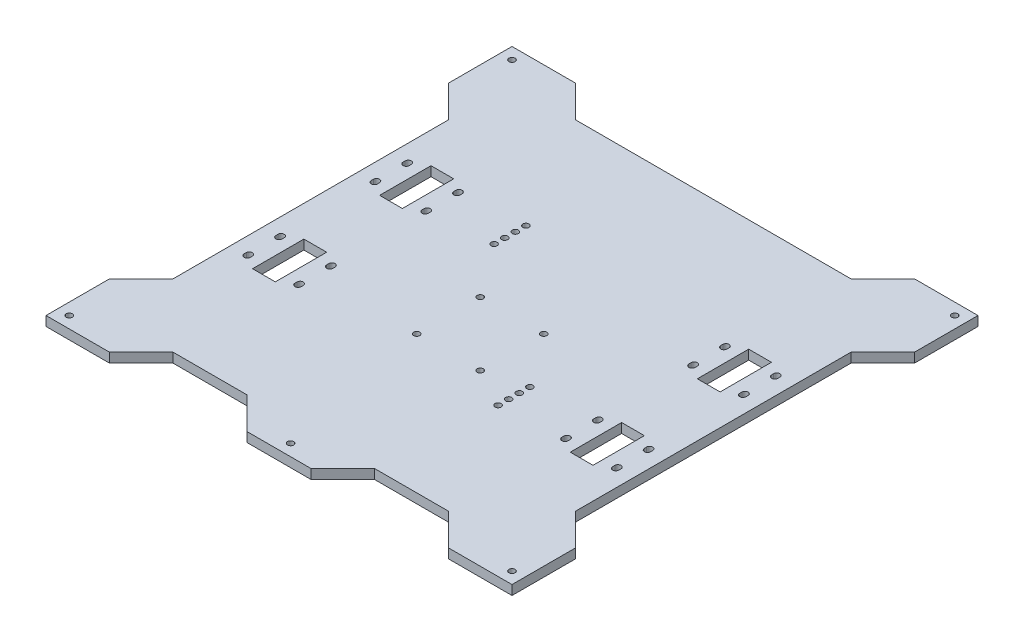
SolidWorks part; units mm, degrees
ref_plane "Front Plane" through (0, 0, 0) normal (0, 0, 1) x (1, 0, 0)
ref_plane "Top Plane" through (0, 0, 0) normal (0, 1, 0) x (1, 0, 0)
ref_plane "Right Plane" through (0, 0, 0) normal (1, 0, 0) x (0, 0, -1)
sketch "Sketch1" plane through (0, 0, 0) normal (0, 1, 0) x (1, 0, 0)
  line L1 (-110, 110) -> (110, 110)
  line L2 (-110, 110) -> (-110, -110)
  line L3 (-110, -110) -> (110, -110)
  line L4 (110, 110) -> (110, -110)
  line L5 (-110, 110) -> (110, -110) construction
  line L6 (-110, -110) -> (110, 110) construction
  point P0 (0, 0)
  dimension "D1" = 220
  dimension "D2" = 220
extrude "Square" add sketch "Sketch1" along normal blind 4.5
sketch "Sketch2" plane through (0, 4.5, 0) normal (0, 1, 0) x (1, 0, 0)
  line L0 (0, 110) -> (0, -110) construction
  line L1 (110, 110) -> (-110, 110) construction
  line L2 (-110, -110) -> (110, -110) construction
  line L3 (-110, 0) -> (110, 0) construction
  line L4 (-110, 110) -> (-110, -110) construction
  line L5 (110, -110) -> (110, 110) construction
  line L6 (75, 110) -> (75, -110) construction
  line L7 (75, 30) -> (0, 30) construction
  line L8 (75, -30) -> (0, -30) construction
  circle A0 centre (87, 38) radius 1.45
  circle A1 centre (87, 22) radius 1.45
  circle A2 centre (63, 22) radius 1.45
  circle A3 centre (63, 38) radius 1.45
  circle A4 centre (-63, 38) radius 1.45
  circle A5 centre (-63, 22) radius 1.45
  circle A6 centre (-87, 22) radius 1.45
  circle A7 centre (-87, 38) radius 1.45
  circle A8 centre (-87, 22) radius 1.45
  circle A9 centre (-87, 38) radius 1.45
  circle A10 centre (-63, 38) radius 1.45
  circle A11 centre (-63, 22) radius 1.45
  circle A12 centre (63, 22) radius 1.45
  circle A13 centre (63, 38) radius 1.45
  circle A14 centre (87, 38) radius 1.45
  circle A15 centre (87, 22) radius 1.45
  circle A16 centre (87, -22) radius 1.45
  circle A17 centre (87, -38) radius 1.45
  circle A18 centre (63, -38) radius 1.45
  circle A19 centre (63, -22) radius 1.45
  circle A20 centre (-63, -22) radius 1.45
  circle A21 centre (-63, -38) radius 1.45
  circle A22 centre (-87, -38) radius 1.45
  circle A23 centre (-87, -22) radius 1.45
  circle A24 centre (-87, -38) radius 1.45
  circle A25 centre (-87, -22) radius 1.45
  circle A26 centre (-63, -22) radius 1.45
  circle A27 centre (-63, -38) radius 1.45
  circle A28 centre (63, -38) radius 1.45
  circle A29 centre (63, -22) radius 1.45
  circle A30 centre (87, -22) radius 1.45
  circle A31 centre (87, -38) radius 1.45
  dimension "D6" = 2.9
  dimension "D7" = 2.9
  dimension "D1" = 75
  dimension "D2" = 30
  dimension "D3" = 16
  dimension "D5" = 12
extrude "LM8UU-Holders" cut sketch "Sketch2" against normal through all contours A7 | A6 | A5 | A4 | A20 | A21 | A22 | A23 | A19 | A18 | A17 | A16 | A1 | A0 | A3 | A2 region at (87, 4.5, -38) region at (87, 4.5, -22) region at (63, 4.5, -22) region at (63, 4.5, -38) region at (-63, 4.5, -38) region at (-63, 4.5, -22) region at (-87, 4.5, -22) region at (-87, 4.5, -38) region at (87, 4.5, 22) region at (87, 4.5, 38) region at (63, 4.5, 38) region at (63, 4.5, 22) region at (-63, 4.5, 22) region at (-63, 4.5, 38) region at (-87, 4.5, 38) region at (-87, 4.5, 22)
sketch "Sketch10" plane through (0, 4.5, 0) normal (0, 1, 0) x (1, 0, 0)
  line L0 (0, 110) -> (0, -79.9796) construction
  line L3 (-26.5242, 0) -> (110, 0) construction
  line L6 (75, 110) -> (75, -110) construction
  line L7 (75, 30) -> (-75, 30) construction
  line L8 (87, 22) -> (87, 23) construction
  line L9 (110, 110) -> (-110, 110) construction
  line L10 (110, -110) -> (110, 110) construction
  line L11 (85.55, 22) -> (85.55, 23)
  line L12 (88.45, 22) -> (88.45, 23)
  line L13 (87, 38) -> (87, 37) construction
  line L14 (88.45, 38) -> (88.45, 37)
  line L15 (85.55, 38) -> (85.55, 37)
  line L16 (63, 38) -> (63, 37) construction
  line L17 (61.55, 38) -> (61.55, 37)
  line L18 (64.45, 38) -> (64.45, 37)
  line L19 (63, 22) -> (63, 23) construction
  line L20 (64.45, 22) -> (64.45, 23)
  line L21 (61.55, 22) -> (61.55, 23)
  line L22 (75, -30) -> (-75, -30) construction
  line L23 (87, -22) -> (87, -23) construction
  line L24 (85.55, -22) -> (85.55, -23)
  line L25 (88.45, -22) -> (88.45, -23)
  line L26 (87, -38) -> (87, -37) construction
  line L27 (88.45, -38) -> (88.45, -37)
  line L28 (85.55, -38) -> (85.55, -37)
  line L29 (63, -38) -> (63, -37) construction
  line L30 (61.55, -38) -> (61.55, -37)
  line L31 (64.45, -38) -> (64.45, -37)
  line L32 (63, -22) -> (63, -23) construction
  line L33 (64.45, -22) -> (64.45, -23)
  line L34 (61.55, -22) -> (61.55, -23)
  line L35 (26.5242, 0) -> (-110, 0) construction
  line L36 (-87, 22) -> (-87, 23) construction
  line L37 (-85.55, 22) -> (-85.55, 23)
  line L38 (-88.45, 22) -> (-88.45, 23)
  line L39 (-87, 38) -> (-87, 37) construction
  line L40 (-88.45, 38) -> (-88.45, 37)
  line L41 (-85.55, 38) -> (-85.55, 37)
  line L42 (-63, 38) -> (-63, 37) construction
  line L43 (-61.55, 38) -> (-61.55, 37)
  line L44 (-64.45, 38) -> (-64.45, 37)
  line L45 (-63, 22) -> (-63, 23) construction
  line L46 (-64.45, 22) -> (-64.45, 23)
  line L47 (-61.55, 22) -> (-61.55, 23)
  line L48 (-87, -22) -> (-87, -23) construction
  line L49 (-85.55, -22) -> (-85.55, -23)
  line L50 (-88.45, -22) -> (-88.45, -23)
  line L51 (-87, -38) -> (-87, -37) construction
  line L52 (-88.45, -38) -> (-88.45, -37)
  line L53 (-85.55, -38) -> (-85.55, -37)
  line L54 (-63, -38) -> (-63, -37) construction
  line L55 (-61.55, -38) -> (-61.55, -37)
  line L56 (-64.45, -38) -> (-64.45, -37)
  line L57 (-63, -22) -> (-63, -23) construction
  line L58 (-64.45, -22) -> (-64.45, -23)
  line L59 (-61.55, -22) -> (-61.55, -23)
  arc A0 (61.55, 38) -> (64.45, 38) centre (63, 38) cw
  arc A1 (88.45, 38) -> (85.55, 38) centre (87, 38) ccw
  arc A2 (85.55, 22) -> (88.45, 22) centre (87, 22) ccw
  arc A3 (88.45, 23) -> (85.55, 23) centre (87, 23) ccw
  arc A4 (85.55, 37) -> (88.45, 37) centre (87, 37) ccw
  arc A5 (64.45, 37) -> (61.55, 37) centre (63, 37) cw
  arc A6 (64.45, 22) -> (61.55, 22) centre (63, 22) cw
  arc A7 (61.55, 23) -> (64.45, 23) centre (63, 23) cw
  arc A8 (85.55, -22) -> (88.45, -22) centre (87, -22) cw
  arc A9 (88.45, -23) -> (85.55, -23) centre (87, -23) cw
  arc A10 (88.45, -38) -> (85.55, -38) centre (87, -38) cw
  arc A11 (85.55, -37) -> (88.45, -37) centre (87, -37) cw
  arc A12 (61.55, -38) -> (64.45, -38) centre (63, -38) ccw
  arc A13 (64.45, -37) -> (61.55, -37) centre (63, -37) ccw
  arc A14 (64.45, -22) -> (61.55, -22) centre (63, -22) ccw
  arc A15 (61.55, -23) -> (64.45, -23) centre (63, -23) ccw
  arc A16 (-85.55, 22) -> (-88.45, 22) centre (-87, 22) cw
  arc A17 (-88.45, 23) -> (-85.55, 23) centre (-87, 23) cw
  arc A18 (-88.45, 38) -> (-85.55, 38) centre (-87, 38) cw
  arc A19 (-85.55, 37) -> (-88.45, 37) centre (-87, 37) cw
  arc A20 (-61.55, 38) -> (-64.45, 38) centre (-63, 38) ccw
  arc A21 (-64.45, 37) -> (-61.55, 37) centre (-63, 37) ccw
  arc A22 (-64.45, 22) -> (-61.55, 22) centre (-63, 22) ccw
  arc A23 (-61.55, 23) -> (-64.45, 23) centre (-63, 23) ccw
  arc A24 (-85.55, -22) -> (-88.45, -22) centre (-87, -22) ccw
  arc A25 (-88.45, -23) -> (-85.55, -23) centre (-87, -23) ccw
  arc A26 (-88.45, -38) -> (-85.55, -38) centre (-87, -38) ccw
  arc A27 (-85.55, -37) -> (-88.45, -37) centre (-87, -37) ccw
  arc A28 (-61.55, -38) -> (-64.45, -38) centre (-63, -38) cw
  arc A29 (-64.45, -37) -> (-61.55, -37) centre (-63, -37) cw
  arc A30 (-64.45, -22) -> (-61.55, -22) centre (-63, -22) cw
  arc A31 (-61.55, -23) -> (-64.45, -23) centre (-63, -23) cw
  point P8 (87, 22.5)
  point P19 (87, 37.5)
  point P28 (63, 37.5)
  point P35 (63, 22.5)
  point P44 (87, -22.5)
  point P51 (87, -37.5)
  point P58 (63, -37.5)
  point P65 (63, -22.5)
  point P73 (0, 30)
  point P74 (0, -30)
  point P76 (-87, 22.5)
  point P83 (-87, 37.5)
  point P90 (-63, 37.5)
  point P97 (-63, 22.5)
  point P104 (-87, -22.5)
  point P111 (-87, -37.5)
  point P118 (-63, -37.5)
  point P125 (-63, -22.5)
  dimension "D1" = 75
  dimension "D2" = 30
  dimension "D3" = 16
  dimension "D5" = 12
  dimension "D4" = 1.45
  dimension "D7" = 1.45
sketch "Sketch3" plane through (0, 4.5, 0) normal (0, 1, 0) x (1, 0, 0)
  line L0 (0, -110) -> (0, 110) construction
  line L1 (-110, -110) -> (110, -110) construction
  line L2 (110, 110) -> (-110, 110) construction
  line L3 (110, -15) -> (-110, -15) construction
  line L6 (15, -30) -> (-15, -30) construction
  line L7 (15, 0) -> (-15, 0) construction
  line L8 (110, -110) -> (110, 110) construction
  line L9 (-110, 110) -> (-110, -110) construction
  line L10 (110, 0) -> (-110, 0) construction
  circle A0 centre (-15, -30) radius 1.45
  circle A1 centre (15, -30) radius 1.45
  circle A2 centre (15, 0) radius 1.45
  circle A3 centre (-15, 0) radius 1.45
  point P16 (0, -30)
  dimension "D1" = 2.9
  dimension "D2" = 15
  dimension "D3" = 15
  dimension "D5" = 15
extrude "DefaultBelt" cut sketch "Sketch3" against normal through all
sketch "Sketch4" plane through (0, 4.5, 0) normal (0, 1, 0) x (1, 0, 0)
  line L0 (0, 110) -> (0, -110) construction
  line L1 (110, 110) -> (-110, 110) construction
  line L2 (-110, -110) -> (110, -110) construction
  line L3 (-15, -1.45) -> (-15, -28.55) construction
  line L4 (15, -28.55) -> (15, -1.45) construction
  line L5 (15, -15) -> (-15, -15) construction
  arc A0 (-0.7348, 6.25) -> (0.7348, 6.25) centre (0, 5) ccw
  arc A1 (0.7348, 6.25) -> (-0.7348, 6.25) centre (0, 7.5) ccw
  arc A2 (0.7348, -36.25) -> (-0.7348, -36.25) centre (0, -37.5) cw
  arc A3 (-0.7348, -36.25) -> (0.7348, -36.25) centre (0, -35) cw
  circle A4 centre (-15, 0) radius 1.45 construction
  circle A5 centre (-15, -30) radius 1.45 construction
  circle A6 centre (15, -30) radius 1.45 construction
  circle A7 centre (15, 0) radius 1.45 construction
  dimension "D1" = 2.9
  dimension "D2" = 2.9
  dimension "D3" = 20
  dimension "D4" = 22.5
extrude "BeltOptions" [suppressed] cut sketch "Sketch4" against normal through all
sketch "Sketch5" plane through (0, 4.5, 0) normal (0, 1, 0) x (1, 0, 0)
  line L0 (-110, 0) -> (110, 0) construction
  line L1 (-110, 110) -> (-110, -110) construction
  line L2 (110, -110) -> (110, 110) construction
  line L3 (0, 110) -> (0, -110) construction
  line L4 (110, 110) -> (-110, 110) construction
  line L5 (-110, 110) -> (-110, 80)
  line L6 (-110, 80) -> (-95, 65)
  line L7 (-95, 65) -> (-95, -65)
  line L8 (0, 0) -> (-110, 110) construction
  line L9 (-65, 95) -> (65, 95)
  line L10 (-80, 110) -> (-65, 95)
  line L11 (-110, 110) -> (-80, 110)
  line L12 (-95, 65) -> (-95, -65)
  line L13 (0, 0) -> (110, 110) construction
  line L14 (95, 65) -> (95, -65)
  line L15 (110, 110) -> (80, 110)
  line L16 (80, 110) -> (65, 95)
  line L17 (95, 65) -> (95, -65)
  line L18 (110, 80) -> (95, 65)
  line L19 (110, 110) -> (110, 80)
  line L20 (0, 0) -> (110, -110) construction
  line L21 (0, 0) -> (-110, -110) construction
  line L22 (110, -110) -> (110, -80)
  line L23 (110, -80) -> (95, -65)
  line L24 (80, -110) -> (65, -95)
  line L25 (110, -110) -> (80, -110)
  line L26 (-110, -110) -> (-80, -110)
  line L27 (-80, -110) -> (-65, -95)
  line L28 (-65, -95) -> (65, -95)
  line L29 (-110, -80) -> (-95, -65)
  line L30 (-110, -110) -> (-110, -80)
  point P24 (0, 95)
  point P32 (95, 0)
  point P35 (-95, 0)
  point P36 (0, -95)
  circle M16 centre (15, -30) radius 1.45
  circle M18 centre (63, 38) radius 1.45
  circle M20 centre (87, 22) radius 1.45
  circle M22 centre (87, -38) radius 1.45
  circle M23 centre (63, -38) radius 1.45
  circle M24 centre (63, -22) radius 1.45
  circle M25 centre (-87, -22) radius 1.45
  circle M26 centre (-87, -38) radius 1.45
  circle M27 centre (-63, -38) radius 1.45
  circle M28 centre (-63, -22) radius 1.45
  circle M29 centre (-63, 38) radius 1.45
  circle M30 centre (-63, 22) radius 1.45
  circle M31 centre (-87, 22) radius 1.45
  circle M32 centre (-87, 38) radius 1.45
  line M33 (110, -110) -> (110, 110)
  line M34 (110, 110) -> (-110, 110)
  line M35 (-110, 110) -> (-110, -110)
  line M36 (-110, -110) -> (110, -110)
  dimension "D1" = 15
  dimension "D2" = 30
  dimension "D3" = 45
  dimension "D4" = 45
extrude "Shaping" cut sketch "Sketch5" against normal blind 10 flip side to cut contours L29 L27 L28 L24 L23 L14 L18 L16 L9 L10 L6 L7 M35 M36 M33 M34 M16 M18 M20 M22 M24 M26 M28 M30 M32 M31 M29 M27 M25 M23 region at (0.037, 4.5, -0.0113)
sketch "Sketch6" plane through (0, 4.5, 0) normal (0, 1, 0) x (1, 0, 0)
  line L0 (-110, 110) -> (110, -110) construction
  line L1 (-110, -110) -> (110, 110) construction
  line L2 (110, 80) -> (110, 110) construction
  line L3 (0, 95) -> (0, -95) construction
  line L4 (-65, 95) -> (65, 95) construction
  line L5 (-65, -95) -> (65, -95) construction
  line L6 (-95, 0) -> (95, 0) construction
  line L7 (-95, 65) -> (-95, -65) construction
  line L8 (95, 65) -> (95, -65) construction
  circle A0 centre (-104.5, 104.5) radius 1.45
  circle A1 centre (104.5, 104.5) radius 1.45
  circle A2 centre (104.5, -104.5) radius 1.45
  circle A3 centre (-104.5, -104.5) radius 1.45
  dimension "D2" = 2.9
  dimension "D1" = 45
  dimension "D3" = 104.5
extrude "Cut-Extrude5" cut sketch "Sketch6" against normal through all
sketch "Sketch7" plane through (0, 4.5, 0) normal (0, 1, 0) x (1, 0, 0)
  line L0 (-87, 38) -> (-63, 22) construction
  line L1 (-63, 22) -> (-87, 22) construction
  line L2 (-87, 22) -> (-63, 38) construction
  line L3 (-63, 38) -> (-87, 38) construction
  line L4 (-95, 0) -> (95, 0) construction
  line L5 (-80.375, 42.125) -> (-69.625, 42.125)
  line L6 (-80.375, 42.125) -> (-80.375, 17.875)
  line L7 (-80.375, 17.875) -> (-69.625, 17.875)
  line L8 (-69.625, 42.125) -> (-69.625, 17.875)
  line L9 (-80.375, 42.125) -> (-69.625, 17.875) construction
  line L10 (-80.375, 17.875) -> (-69.625, 42.125) construction
  line L11 (-95, 65) -> (-95, -65) construction
  line L12 (95, 65) -> (95, -65) construction
  line L13 (0, -95) -> (0, 95) construction
  line L14 (-65, -95) -> (65, -95) construction
  line L15 (-65, 95) -> (65, 95) construction
  line L16 (-80.375, -17.875) -> (-69.625, -42.125) construction
  line L17 (-80.375, -42.125) -> (-69.625, -17.875) construction
  line L18 (-63, -38) -> (-87, -38) construction
  line L19 (-87, -22) -> (-63, -38) construction
  line L20 (-63, -22) -> (-87, -22) construction
  line L21 (-87, -38) -> (-63, -22) construction
  line L22 (-69.625, -42.125) -> (-69.625, -17.875)
  line L23 (-80.375, -17.875) -> (-69.625, -17.875)
  line L24 (-80.375, -42.125) -> (-80.375, -17.875)
  line L25 (-80.375, -42.125) -> (-69.625, -42.125)
  line L26 (-80.375, 17.875) -> (-69.625, 42.125) construction
  line L27 (80.375, 17.875) -> (69.625, 42.125) construction
  line L28 (87, -38) -> (63, -22) construction
  line L29 (63, -22) -> (87, -22) construction
  line L30 (87, -22) -> (63, -38) construction
  line L31 (63, -38) -> (87, -38) construction
  line L32 (80.375, -42.125) -> (69.625, -17.875) construction
  line L33 (80.375, -17.875) -> (69.625, -42.125) construction
  line L34 (80.375, 17.875) -> (69.625, 42.125) construction
  line L35 (80.375, 42.125) -> (69.625, 17.875) construction
  line L36 (63, 38) -> (87, 38) construction
  line L37 (87, 22) -> (63, 38) construction
  line L38 (63, 22) -> (87, 22) construction
  line L39 (87, 38) -> (63, 22) construction
  line L40 (80.375, -42.125) -> (69.625, -42.125)
  line L41 (80.375, -42.125) -> (80.375, -17.875)
  line L42 (80.375, -17.875) -> (69.625, -17.875)
  line L43 (69.625, -42.125) -> (69.625, -17.875)
  line L44 (69.625, 42.125) -> (69.625, 17.875)
  line L45 (80.375, 17.875) -> (69.625, 17.875)
  line L46 (80.375, 42.125) -> (80.375, 17.875)
  line L47 (80.375, 42.125) -> (69.625, 42.125)
  point P4 (-75, 30)
  point P33 (-75, -30)
  point P50 (75, -30)
  point P51 (75, 30)
  dimension "D1" = 10.75
  dimension "D2" = 24.25
extrude "Cut-Extrude6" cut sketch "Sketch7" against normal through all
sketch "Sketch8" plane through (0, 4.5, 0) normal (0, 1, 0) x (1, 0, 0)
  line L0 (0, 0) -> (0, 95) construction
  line L1 (0, 0) -> (-66.8115, 0) construction
  line L2 (-65, -95) -> (65, -95) construction
  line L3 (-65, 95) -> (65, 95) construction
  line L4 (-33.45, 40) -> (-33.45, 25) construction
  line L5 (-33.45, 40) -> (-33.45, 25) construction
  line L6 (33.45, -40) -> (33.45, -25) construction
  circle A0 centre (-33.45, 40) radius 1.45
  circle A1 centre (-33.45, 35) radius 1.45
  circle A2 centre (-33.45, 30) radius 1.45
  circle A3 centre (-33.45, 25) radius 1.45
  circle A8 centre (33.45, -40) radius 1.45
  circle A9 centre (33.45, -35) radius 1.45
  circle A10 centre (33.45, -30) radius 1.45
  circle A11 centre (33.45, -25) radius 1.45
  dimension "D1" = 2.9
  dimension "D11" = 2.9
  dimension "D12" = 2.9
  dimension "D13" = 2.9
  dimension "D14" = 2.9
  dimension "D2" = 55
  dimension "D4" = 33.45
  dimension "D5" = 5
  dimension "D6" = 5
  dimension "D7" = 55
  dimension "D8" = 5
  dimension "D9" = 5
  dimension "D10" = 33.45
extrude "EndstopTrigger" cut sketch "Sketch8" against normal through all
pattern_linear "LPattern1" [suppressed] count 2 spacing 30 of bodies 108
sketch "Sketch9" plane through (0, 4.5, 0) normal (0, 1, 0) x (1, 0, 0)
  line L2 (-80, -110) -> (80, -110) construction
  line L3 (0, -110) -> (0, -95) construction
  line L4 (-104.5, -104.5) -> (104.5, -104.5) construction
  line L5 (15, -110) -> (-15, -110)
  line L6 (-15, -110) -> (-30, -95)
  line L7 (-95, 0) -> (95, 0) construction
  line L8 (-95, 65) -> (-95, -65) construction
  line L9 (-30, -95) -> (30, -95)
  line L10 (15, -110) -> (30, -95)
  line L11 (95, 65) -> (95, -65) construction
  line L12 (-110, -110) -> (-80, -110) construction
  line L13 (-65, -95) -> (65, -95) construction
  line L14 (-80, -110) -> (-65, -95) construction
  line L15 (80, -110) -> (65, -95) construction
  circle A0 centre (0, -104.5) radius 1.45
  circle A3 centre (-104.5, -104.5) radius 1.45 construction
  circle A4 centre (104.5, -104.5) radius 1.45 construction
extrude "Boss-Extrude1" add sketch "Sketch9" against normal through all
extrude "HolesToSlots" cut sketch "Sketch10" against normal through all
sketch "Sketch11" plane through (0, 4.5, 0) normal (0, 1, 0) x (1, 0, 0)
  line L0 (0, -110) -> (0, 0) construction
  line L1 (-65, -95) -> (-30, -95) construction
  line L2 (95, 0) -> (0, 0) construction
  line L3 (95, 65) -> (95, -65) construction
  line L4 (0, 0) -> (110, -110) construction
  line L5 (-69.1421, -85) -> (-5, -85)
  line L6 (-69.1421, -85) -> (-84.1421, -100)
  line L7 (-84.1421, -100) -> (-100, -100)
  line L8 (-100, -100) -> (-100, -84.1421)
  line L9 (-100, -84.1421) -> (-85, -69.1421)
  line L10 (-85, -69.1421) -> (-85, -52.125)
  line L11 (-85, -52.125) -> (-5, -52.125)
  line L12 (-80, -110) -> (-65, -95) construction
  line L13 (-110, -80) -> (-95, -65) construction
  line L14 (-110, -80) -> (-110, -110) construction
  line L15 (-110, -110) -> (-80, -110) construction
  line L16 (-80.375, -42.125) -> (-69.625, -42.125) construction
  line L17 (-95, 65) -> (-95, -65) construction
  line L18 (-5, -52.125) -> (-5, -85)
  line L19 (5, -52.125) -> (5, -85)
  line L20 (85, -52.125) -> (5, -52.125)
  line L21 (85, -69.1421) -> (85, -52.125)
  line L22 (100, -84.1421) -> (85, -69.1421)
  line L23 (100, -100) -> (100, -84.1421)
  line L24 (84.1421, -100) -> (100, -100)
  line L25 (69.1421, -85) -> (84.1421, -100)
  line L26 (69.1421, -85) -> (5, -85)
  line L27 (69.1421, 85) -> (5, 85)
  line L28 (69.1421, 85) -> (84.1421, 100)
  line L29 (84.1421, 100) -> (100, 100)
  line L30 (100, 100) -> (100, 84.1421)
  line L31 (100, 84.1421) -> (85, 69.1421)
  line L32 (85, 69.1421) -> (85, 52.125)
  line L33 (85, 52.125) -> (5, 52.125)
  line L34 (5, 52.125) -> (5, 85)
  line L35 (-5, 52.125) -> (-5, 85)
  line L36 (-85, 52.125) -> (-5, 52.125)
  line L37 (-85, 69.1421) -> (-85, 52.125)
  line L38 (-100, 84.1421) -> (-85, 69.1421)
  line L39 (-100, 100) -> (-100, 84.1421)
  line L40 (-84.1421, 100) -> (-100, 100)
  line L41 (-69.1421, 85) -> (-84.1421, 100)
  line L42 (-69.1421, 85) -> (-5, 85)
  line L43 (-15, -110) -> (15, -110) construction
  dimension "D1" = 10
  dimension "D2" = 10
  dimension "D3" = 10
  dimension "D4" = 10
  dimension "D5" = 10
  dimension "D6" = 10
  dimension "D7" = 10
  dimension "D8" = 5
extrude "Cut-Extrude7" [suppressed] cut sketch "Sketch11" against normal through all
sketch "Sketch12" [suppressed] plane through (0, 4.5, 0) normal (0, 1, 0) x (1, 0, 0)
  line L0 (0, 0) -> (-110, -110) construction
  line L1 (-110, -110) -> (-80, -110) construction
  line L2 (-110, -80) -> (80, 110) construction
  line L3 (110, 80) -> (-80, -110) construction
  line L4 (-95, -65) -> (-65, -95) construction
  line L5 (0, 0) -> (0, -95) construction
  line L6 (-65, -95) -> (65, -95) construction
  line L7 (95, 0) -> (-95, 0) construction
  line L8 (-95, 65) -> (-95, -65) construction
  line L9 (-100, -100) -> (-100, -84.1421)
  line L10 (-100, -84.1421) -> (-59.2893, -43.4315)
  line L11 (-59.2893, -43.4315) -> (-43.4315, -43.4315)
  line L12 (-110, -80) -> (-110, -110) construction
  line L13 (-100, -100) -> (-84.1421, -100)
  line L14 (-84.1421, -100) -> (-43.4315, -59.2893)
  line L15 (-43.4315, -59.2893) -> (-43.4315, -43.4315)
  line L16 (55, -85) -> (-55, -85)
  line L17 (-55, -85) -> (-29.2893, -59.2893)
  line L18 (-29.2893, -59.2893) -> (29.2893, -59.2893)
  line L19 (95, -65) -> (65, -95) construction
  line L20 (0, 0) -> (110, -110) construction
  line L21 (55, -85) -> (29.2893, -59.2893)
  line L22 (43.4315, -59.2893) -> (43.4315, -43.4315)
  line L23 (84.1421, -100) -> (43.4315, -59.2893)
  line L24 (100, -100) -> (84.1421, -100)
  line L25 (59.2893, -43.4315) -> (43.4315, -43.4315)
  line L26 (100, -84.1421) -> (59.2893, -43.4315)
  line L27 (100, -100) -> (100, -84.1421)
  line L28 (95, 65) -> (65, 95) construction
  line L29 (-95, 65) -> (-65, 95) construction
  line L30 (100, 100) -> (100, 84.1421)
  line L31 (100, 84.1421) -> (59.2893, 43.4315)
  line L32 (59.2893, 43.4315) -> (43.4315, 43.4315)
  line L33 (100, 100) -> (84.1421, 100)
  line L34 (84.1421, 100) -> (43.4315, 59.2893)
  line L35 (43.4315, 59.2893) -> (43.4315, 43.4315)
  line L36 (55, 85) -> (29.2893, 59.2893)
  line L37 (-29.2893, 59.2893) -> (29.2893, 59.2893)
  line L38 (-55, 85) -> (-29.2893, 59.2893)
  line L39 (55, 85) -> (-55, 85)
  line L40 (-43.4315, 59.2893) -> (-43.4315, 43.4315)
  line L41 (-84.1421, 100) -> (-43.4315, 59.2893)
  line L42 (-100, 100) -> (-84.1421, 100)
  line L43 (-59.2893, 43.4315) -> (-43.4315, 43.4315)
  line L44 (-100, 84.1421) -> (-59.2893, 43.4315)
  line L45 (-100, 100) -> (-100, 84.1421)
  point P40 (0, -59.2893)
  point P41 (0, -85)
  point P67 (0, 85)
  point P68 (0, 59.2893)
  dimension "D1" = 10
  dimension "D2" = 10
  dimension "D3" = 80
  dimension "D4" = 10
  dimension "D5" = 10
  dimension "D6" = 0
extrude "Cut-Extrude8" [suppressed] cut sketch "Sketch12" against normal through all
sketch "Sketch14" [suppressed] plane through (0, 4.5, 0) normal (0, 1, 0) x (1, 0, 0)
  line L0 (0, 85) -> (0, 110) construction
  line L1 (55, 85) -> (-55, 85) construction
  line L2 (15, 110) -> (-15, 110) construction
  line L3 (10.8579, 100) -> (-10.8579, 100)
  line L4 (-10.8579, 100) -> (-25.8579, 85)
  line L5 (-25.8579, 85) -> (25.8579, 85)
  line L6 (-15, 110) -> (-30, 95) construction
  line L7 (10.8579, 100) -> (25.8579, 85)
  point P13 (0, 100)
  dimension "D1" = 10
  dimension "D2" = 10
extrude "Cut-Extrude10" [suppressed] cut sketch "Sketch14" against normal through all
sketch "Sketch13" [suppressed] plane through (0, 4.5, 0) normal (0, 1, 0) x (1, 0, 0)
  line L0 (-59.2893, 43.4315) -> (-59.2893, -43.4315) construction
  line L1 (-100, 84.1421) -> (-59.2893, 43.4315) construction
  line L2 (-59.2893, 0) -> (0, 0) construction
  line L3 (-59.2893, 33.4315) -> (-59.2893, -33.4315)
  line L4 (-59.2893, -33.4315) -> (-43.4315, -33.4315)
  line L5 (-43.4315, -33.4315) -> (-43.4315, 33.4315)
  line L6 (-43.4315, 33.4315) -> (-59.2893, 33.4315)
  line L7 (-59.2893, 43.4315) -> (-43.4315, 43.4315) construction
  line L8 (-43.4315, -43.4315) -> (-59.2893, -43.4315) construction
  line L9 (-43.4315, 43.4315) -> (-43.4315, 59.2893) construction
  line L10 (0, 0) -> (0, 43.4315) construction
  line L11 (59.2893, 43.4315) -> (59.2893, -43.4315) construction
  line L12 (43.4315, 33.4315) -> (59.2893, 33.4315)
  line L13 (43.4315, -33.4315) -> (43.4315, 33.4315)
  line L14 (59.2893, -33.4315) -> (43.4315, -33.4315)
  line L15 (59.2893, 33.4315) -> (59.2893, -33.4315)
  line L16 (110, -110) -> (0, 0) construction
  line L17 (55, -85) -> (29.2893, -59.2893) construction
  line L18 (-33.4315, -43.2893) -> (33.4315, -43.2893)
  line L19 (-33.4315, -43.2893) -> (-33.4315, -63.4315)
  line L20 (-33.4315, -63.4315) -> (33.4315, -63.4315)
  line L21 (33.4315, -43.2893) -> (33.4315, -63.4315)
  line L22 (-33.4315, -43.2893) -> (33.4315, -63.4315) construction
  line L23 (-33.4315, -63.4315) -> (33.4315, -43.2893) construction
  line L24 (-43.4315, -59.2893) -> (-43.4315, -43.4315) construction
  line L25 (0, -53.3604) -> (0, -63.4315) construction
  line L26 (55, 85) -> (25.8579, 85) construction
  line L28 (43.4315, -43.4315) -> (43.4315, -59.2893) construction
  line L29 (29.2893, -59.2893) -> (-29.2893, -59.2893) construction
  line L30 (43.4315, 59.2893) -> (43.4315, 43.4315) construction
  line L31 (-33.4315, 83) -> (33.4315, 83)
  line L32 (-33.4315, 83) -> (-33.4315, 15)
  line L33 (-33.4315, 15) -> (33.4315, 15)
  line L34 (33.4315, 83) -> (33.4315, 15)
  line L35 (-33.4315, 83) -> (33.4315, 15) construction
  line L36 (-33.4315, 15) -> (33.4315, 83) construction
  point P27 (0, -53.3604)
  point P43 (0, 49)
  dimension "D1" = 10
  dimension "D2" = 10
  dimension "D3" = 10
  dimension "D4" = 10
  dimension "D5" = 16
  dimension "D6" = 10
  dimension "D7" = 10
  dimension "D8" = 15
  dimension "D9" = 2
extrude "Cut-Extrude9" [suppressed] cut sketch "Sketch13" against normal through all
sketch "Sketch15" [suppressed] plane through (0, 4.5, 0) normal (0, 1, 0) x (1, 0, 0)
  line L0 (-59.2893, 0) -> (-95, 0) construction
  line L1 (-59.2893, 33.4315) -> (-59.2893, -33.4315) construction
  line L2 (-95, 65) -> (-95, -65) construction
  line L3 (-80.5, 17.875) -> (-69.5, 17.875) construction
  line L4 (-59.2893, -15) -> (-59.2893, -7.875)
  line L5 (-85, -7.875) -> (-85, 7.875)
  line L6 (-85, 7.875) -> (-66.4143, 7.875)
  line L7 (-59.2893, -7.875) -> (-59.2893, 7.875)
  line L8 (-66.4143, -7.875) -> (-59.2893, -15)
  line L9 (-85, -7.875) -> (-66.4143, -7.875)
  line L11 (-66.4143, 7.875) -> (-59.2893, 15)
  line L12 (-59.2893, 15) -> (-59.2893, 7.875)
  line L13 (0, 0) -> (0, -21.7485) construction
  line L14 (59.2893, 0) -> (95, 0) construction
  line L15 (59.2893, 15) -> (59.2893, 7.875)
  line L16 (66.4143, 7.875) -> (59.2893, 15)
  line L17 (85, -7.875) -> (66.4143, -7.875)
  line L18 (66.4143, -7.875) -> (59.2893, -15)
  line L19 (59.2893, -7.875) -> (59.2893, 7.875)
  line L20 (85, 7.875) -> (66.4143, 7.875)
  line L21 (85, -7.875) -> (85, 7.875)
  line L22 (59.2893, -15) -> (59.2893, -7.875)
  line L23 (-59.2893, 0) -> (-95, 0) construction
  point P17 (-85, 0)
  point P30 (85, 0)
  dimension "D1" = 10
  dimension "D2" = 10
  dimension "D4" = 45
  dimension "D5" = 15
extrude "Cut-Extrude11" [suppressed] cut sketch "Sketch15" against normal through all
sketch "Sketch16" [suppressed] plane through (0, 4.5, 0) normal (0, 1, 0) x (1, 0, 0)
  line L0 (-85, -69.1421) -> (-85, -52.125)
  line L1 (-59.2893, -43.4315) -> (-100, -84.1421) construction
  line L2 (-85, -52.125) -> (-67.9829, -52.125)
  line L3 (-67.9829, -52.125) -> (-85, -69.1421)
  line L4 (-95, 65) -> (-95, -65) construction
  line L5 (-80.5, -42.125) -> (-69.5, -42.125) construction
  line L6 (-95, 0) -> (95, 0) construction
  line L7 (95, 65) -> (95, -65) construction
  line L8 (0, 0) -> (0, -95) construction
  line L9 (-65, -95) -> (65, -95) construction
  line L10 (-67.9829, 52.125) -> (-85, 69.1421)
  line L11 (-85, 52.125) -> (-67.9829, 52.125)
  line L12 (-85, 69.1421) -> (-85, 52.125)
  line L13 (-67.9829, -52.125) -> (-85, -69.1421)
  line L14 (67.9829, -52.125) -> (85, -69.1421)
  line L15 (85, 69.1421) -> (85, 52.125)
  line L16 (85, 52.125) -> (67.9829, 52.125)
  line L17 (67.9829, 52.125) -> (85, 69.1421)
  line L18 (67.9829, -52.125) -> (85, -69.1421)
  line L19 (85, -52.125) -> (67.9829, -52.125)
  line L20 (85, -69.1421) -> (85, -52.125)
  line L21 (100, -84.1421) -> (59.2893, -43.4315) construction
  line L23 (69.5, -42.125) -> (80.5, -42.125) construction
  line L24 (80.5, 42.125) -> (69.5, 42.125) construction
  line L25 (59.2893, 43.4315) -> (100, 84.1421) construction
  line L26 (-100, 84.1421) -> (-59.2893, 43.4315) construction
  line L27 (-69.5, 42.125) -> (-80.5, 42.125) construction
  dimension "D1" = 10
  dimension "D2" = 10
  dimension "D3" = 10
  dimension "D4" = 10
  dimension "D5" = 10
  dimension "D6" = 10
  dimension "D7" = 10
  dimension "D8" = 10
extrude "Cut-Extrude12" [suppressed] cut sketch "Sketch16" against normal through all contours L3 L2 L0 | L10 L12 L11 | L17 L16 L15 | L14 L20 L19
sketch "Sketch17" [suppressed] plane through (0, 4.5, 0) normal (0, 1, 0) x (1, 0, 0)
  line L0 (-80, -110) -> (110, 80) construction
  line L1 (-110, -110) -> (-80, -110) construction
  line L2 (80, 110) -> (-110, -80) construction
  line L3 (-110, 80) -> (80, -110) construction
  line L4 (-80, 110) -> (110, -80) construction
  line L5 (0, 0) -> (0, 110) construction
  line L6 (15, 110) -> (-15, 110) construction
  line L7 (0, 0) -> (-95, 0) construction
  line L8 (-95, 65) -> (-95, -65) construction
  line L9 (-97.6777, 78.9914) -> (-59.7954, 41.1091)
  line L10 (-59.7954, 41.1091) -> (-41.1091, 41.1091)
  line L11 (-41.1091, 41.1091) -> (-41.1091, 59.7954)
  line L12 (-41.1091, 59.7954) -> (-78.9914, 97.6777)
  line L13 (-97.6777, 97.6777) -> (-78.9914, 97.6777)
  line L14 (-60.0503, 78.7365) -> (-78.7365, 60.0503) construction
  line L15 (-97.6777, 78.9914) -> (-97.6777, 97.6777)
  line L16 (0, 87) -> (-45.6863, 87)
  line L17 (-45.6863, 87) -> (0, 41.3137)
  line L18 (-65, 95) -> (-30, 95) construction
  line L19 (0, 87) -> (0, 41.3137)
  dimension "D1" = 15
  dimension "D2" = 8
  dimension "D3" = 8
  dimension "D4" = 40
  dimension "D5" = 8
  dimension "D6" = 8
extrude "Cut-Extrude13" [suppressed] cut sketch "Sketch17" against normal through all
mirror "Mirror1" [suppressed] about plane through (0, 0, 0) normal (1, 0, 0)
mirror "Mirror2" [suppressed] about plane through (0, 0, 0) normal (0, 0, 1)
equation "\"X-ROD-SPACING\"=45"
equation "\"Y-ROD-SPACING\"=75"
equation "\"Z-ROD-SPACING\"=17.5"
equation "\"Y-BED-OFFSET\"=2"
equation "\"Y-BED-ROD-INSET\"=3.5"
equation "\"T-SLOT-NUT-FILLET-RADIUS\"=0.5"
equation "\"T-SLOT-SCREW-SHAFT-RADIUS\"=1.55"
equation "\"T-SLOT-SCREW-SHAFT-CUTOUT-LENGTH\"=11"
equation "\"T-SLOT-NUT-DEPTH\"=3.5"
equation "\"T-SLOT-NUT-WIDTH\"=2.85"
equation "\"T-SLOT-NUT-END-DISTANCE\"=8"
equation "\"ACRYLIC-THICKNESS\"=10"
equation "\"ACRYLIC-THICKNESS2\"=4.5"
equation "\"ACRYLIC-TAB-CUTOUT-SIZE\"=\"ACRYLIC-THICKNESS\"+\"ACRYLIC-TAB-TOLERANCE\"*2"
equation "\"ACRYLIC-TAB-WIDTH\"=\"ACRYLIC-THICKNESS\""
equation "\"ACRYLIC-M3-HOLE\"=2.9"
equation "\"SMOOTHROD-CAP-SCREW-DISTANCE\"=20"
equation "\"FRAME-WIDTH-INNER\"=370"
equation "\"NEMA17-HOLE-SPACING\"=31"
equation "\"NEMA17-CENTRAL-CUTOUT\"=22.5"
equation "\"Z-BRACKET-REACH\"=57"
equation "\"TOP-BRACKET-SPACING\"=40"
equation "\"SMOOTHROD-X-LENGTH\"=350"
equation "\"SMOOTHROD-Y-LENGTH\"=350"
equation "\"SMOOTHROD-Z-LENGTH\"=350"
equation "\"SMOOTHROD-TIGHTENING-HEADROOM\"=.25"
equation "\"LEADSCREW-Z-LENGTH\"=300"
equation "\"SCREW-LENGTH-FRAME\"=\"ACRYLIC-THICKNESS\" + 10"
equation "\"SCREW-HEAD-RADIUS\"=6"
equation "\"PRINTED-X-SMOOTHROD-DIAMETER\"=8.8"
equation "\"PRINTED-X-SMOOTHROD-CUTOUT\"=10"
equation "\"PRINTED-X-BASE-HEIGHT\"=10"
equation "\"PRINTED-LM8UU-CUTOUT-SIZE\"=15.5"
equation "\"PRINTED-LM8UU-CUTOUT-LENGTH\"=24.5"
equation "\"PRINTED-X-IDLER-HEIGHT\"=16"
equation "\"PSU-MOUNTING-WIDTH\"=95"
equation "\"PSU-MOUNTING-HEIGHT\"=177"
equation "\"Y-BELT-TO-ROD-DISTANCE\"=20"
equation "\"D6@Sketch2\"=\"ACRYLIC-M3-HOLE\""
equation "\"D7@Sketch2\"=\"ACRYLIC-M3-HOLE\""
equation "\"D1@Sketch2\"=\"Y-ROD-SPACING\""
equation "\"D1@Sketch3\"=\"ACRYLIC-M3-HOLE\""
equation "\"D2@Sketch6\"=\"ACRYLIC-M3-HOLE\""
equation "\"Y-BED-SCREW-SPACING\"=209"
equation "\"Y-BED-SCREW-CUTOUT-SLOT-HEIGHT\"=2.5"
equation "\"ACRYLIC-TAB-TOLERANCE\"=-.05"
equation "\"Z-ROD-INSET\"=13.5"
equation "\"SCREW-LENGTH-MOTOR\"=\"ACRYLIC-THICKNESS\" + 5"
equation "\"SCREW-LENGTH-EXTRUDER\"=28"
equation "\"PRINTED-M3-HOLE\"=3.5"
equation "\"SPOOL-HOLDER-ROD-SPACING\"=150"
equation "\"ACRYLIC-X-CARRIAGE-WIDTH\"=55"
equation "\"ACRYLIC-X-CARRIAGE-HEIGHT\"=75"
equation "\"ACRYLIC-X-CARRIAGE-LM8UU-CUTOUT-WIDTH\"=24.25"
equation "\"ACRYLIC-X-CARRIAGE-LM8UU-CUTOUT-HEIGHT\"=11.0"
equation "\"ACRYLIC-X-CARRIAGE-SCREW-SPACING-X\"=15"
equation "\"ACRYLIC-X-CARRIAGE-SCREW-SPACING-Y\"=33"
equation "\"ACRYLIC-X-CARRIAGE-CENTER-TAB-SPACING\"=14"
equation "\"ACRYLIC-X-CARRIAGE-EXTRUDER-OFFSET\"=26"
equation "\"ACRYLIC-X-CARRIAGE-EXTRUDER-ANGLE\"=90"
equation "\"ACRYLIC-X-CARRIAGE-EXTRUDER-SHELF-DEPTH\"=\"ACRYLIC-X-CARRIAGE-EXTRUDER-OFFSET\" + 28"
equation "\"ACRYLIC-X-CARRIAGE-EXTRUDER-BRACE-SPACING\"=23"
equation "\"ACRYLIC-X-CARRIAGE-EXTRUDER-BRACE-TAB-OFFSET\"=20"
equation "\"ACRYLIC-X-CARRIAGE-EXTRUDER-BRACE-HEIGHT\"=35"
equation "\"ACRYLIC-X-CARRIAGE-EXTRUDER-BRACE-SCREW-SPACING\"=22"
equation "\"ACRYLIC-X-CARRIAGE-DUAL-WIDTH-MULTIPLIER\"=1.65"
equation "\"ACRYLIC-X-CARRIAGE-DUAL-HOTEND-SPACING\"=42"
equation "\"ACRYLIC-X-CARRIAGE-DUAL-WIDTH\"=75"
equation "\"ACRYLIC-X-CARRIAGE-DUAL-HOTEND-SEPARATION\"=36"
equation "\"ACRYLIC-X-CARRIAGE-DUAL-MOUNT-PLATE-DEPTH\"=75"
equation "\"ACRYLIC-X-CARRIAGE-DUAL-MOUNT-BRACE-WIDTH\"=33"
equation "\"ACRYLIC-X-CARRIAGE-DUAL-MOUNT-SCREW-WIDTH\"=40"
equation "\"BLOWER-FAN-WIDTH\"=15"
equation "\"D2@Sketch7\"=\"ACRYLIC-X-CARRIAGE-LM8UU-CUTOUT-WIDTH\""
equation "\"D1@Sketch8\"=\"ACRYLIC-M3-HOLE\""
equation "\"D2@Sketch4\"=\"ACRYLIC-M3-HOLE\""
equation "\"D1@Sketch4\"=\"ACRYLIC-M3-HOLE\""
equation "\"D3@Sketch4\"=20"
equation "\"D4@Sketch10\"=\"ACRYLIC-M3-HOLE\"/2"
equation "\"D7@Sketch10\"=\"ACRYLIC-M3-HOLE\" / 2"
equation "\"D11@Sketch8\"=\"ACRYLIC-M3-HOLE\""
equation "\"D12@Sketch8\"=\"ACRYLIC-M3-HOLE\""
equation "\"D13@Sketch8\"=\"ACRYLIC-M3-HOLE\""
equation "\"D14@Sketch8\"=\"ACRYLIC-M3-HOLE\""
